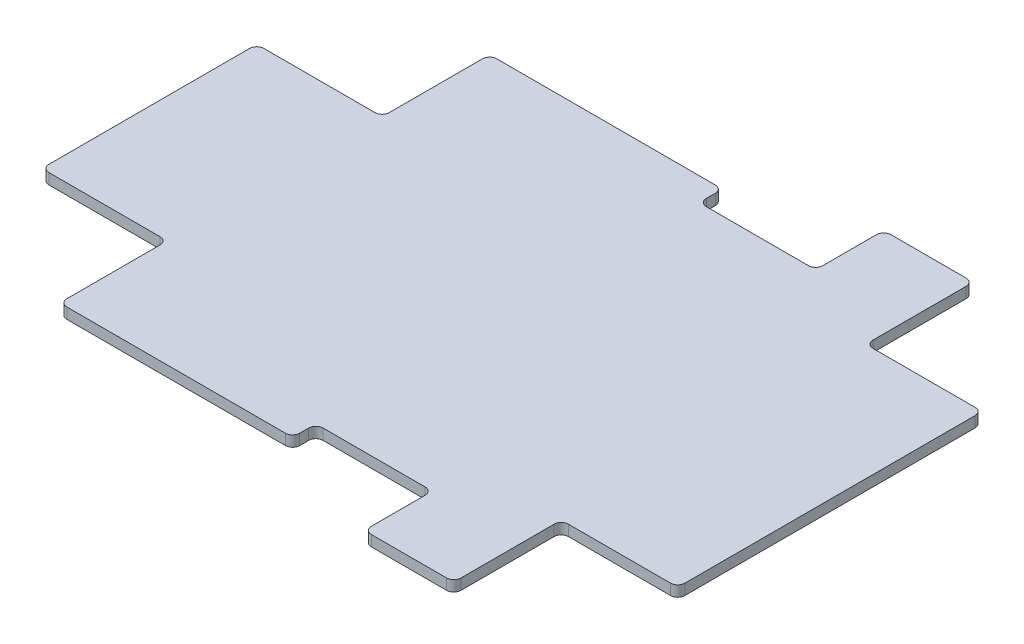
SolidWorks part; units mm, degrees
material "Aleación 1060"
ref_plane "Alzado" through (0, 0, 0) normal (0, 0, 1) x (1, 0, 0)
ref_plane "Planta" through (0, 0, 0) normal (0, 1, 0) x (1, 0, 0)
ref_plane "Vista lateral" through (0, 0, 0) normal (1, 0, 0) x (0, 0, -1)
sketch "Croquis1" plane through (0, 0, 0) normal (0, 1, 0) x (1, 0, 0)
  line L0 (0, 0) -> (-380, 0)
  line L1 (-380, 0) -> (-380, 60)
  line L2 (-380, 60) -> (-310, 60)
  line L3 (-310, 60) -> (-310, 120)
  line L4 (-310, 120) -> (-180, 120)
  line L5 (-180, 120) -> (-180, 107)
  line L6 (-180, 107) -> (-115, 107)
  line L7 (-115, 107) -> (-115, 145)
  line L8 (-115, 145) -> (-65, 145)
  line L9 (-65, 145) -> (-65, 85)
  line L10 (0, 0) -> (0, 85)
  line L11 (0, 85) -> (-65, 85)
  dimension "D1" = 380
  dimension "D2" = 60
  dimension "D3" = 70
  dimension "D4" = 120
  dimension "D5" = 130
  dimension "D6" = 13
  dimension "D7" = 50
  dimension "D8" = 85
  dimension "D9" = 65
  dimension "D10" = 60
extrude "Saliente-Extruir1" add sketch "Croquis1" along normal blind 6
mirror "Simetría1" about plane through (0, 6, 0) normal (0, 0, -1) of "Saliente-Extruir1"
fillet "Redondeo1" radius 4 20 edges at (-380, 3, -60) (-310, 3, -60) (-310, 3, -120) (-180, 3, -120) (-180, 3, -107) (-115, 3, -107) (-115, 3, -145) (-65, 3, -85) (-65, 3, -145) (0, 3, -85) (0, 3, 85) (-65, 3, 85) (-65, 3, 145) (-115, 3, 145) (-115, 3, 107) (-180, 3, 107) (-180, 3, 120) (-310, 3, 120) (-310, 3, 60) (-380, 3, 60)
sketch "Croquis2" plane through (0, 6, 0) normal (0, 1, 0) x (1, 0, 0)
  line L0 (-380, 0) -> (0, 0) construction
  line L1 (-380, 56) -> (-380, -56) construction
  line L2 (0, -81) -> (0, 81) construction
  line L3 (-214.7209, -131) -> (31.1095, -131) construction
  line L4 (-214.0485, -154) -> (44.3152, -154) construction
  line L5 (-69, -145) -> (-111, -145) construction
  line L6 (-34, -177) -> (-146, -177)
  line L7 (-34, -177) -> (-34, -131)
  line L8 (-34, -131) -> (-146, -131)
  line L9 (-146, -177) -> (-146, -131)
  line L10 (-34, -177) -> (-146, -131) construction
  line L11 (-34, -131) -> (-146, -177) construction
  line L13 (-364, -177) -> (-476, -177)
  line L14 (-364, -177) -> (-364, -131)
  line L15 (-364, -131) -> (-476, -131)
  line L16 (-476, -177) -> (-476, -131)
  line L17 (-364, -177) -> (-476, -131) construction
  line L18 (-364, -131) -> (-476, -177) construction
  line L19 (-34, 177) -> (-146, 177)
  line L20 (-34, 177) -> (-34, 131)
  line L21 (-34, 131) -> (-146, 131)
  line L22 (-146, 177) -> (-146, 131)
  line L23 (-364, 131) -> (-476, 177) construction
  line L24 (-364, 177) -> (-476, 131) construction
  line L25 (-476, 177) -> (-476, 131)
  line L26 (-364, 131) -> (-476, 131)
  line L27 (-364, 177) -> (-364, 131)
  line L28 (-364, 177) -> (-476, 177)
  point P10 (-90, -154)
  point P17 (-90, -145)
  point P20 (-420, -154)
  point P33 (-420, 154)
  dimension "D1" = 131
  dimension "D2" = 154
  dimension "D3" = 46
  dimension "D4" = 112
  dimension "D5" = 330
sketch "Croquis3" plane through (0, 6, 0) normal (0, 1, 0) x (1, 0, 0)
  line L0 (-90, -145) -> (-90, 145) construction
  line L1 (-69, -145) -> (-111, -145) construction
  line L2 (-69, 145) -> (-111, 145) construction
  line L3 (-151.9, 16.8885) -> (-151.9, -25.475) construction
  line L4 (-222.2, 27.5722) -> (-222.2, -25.475) construction
  dimension "D1" = 132.2
  dimension "D2" = 61.9
